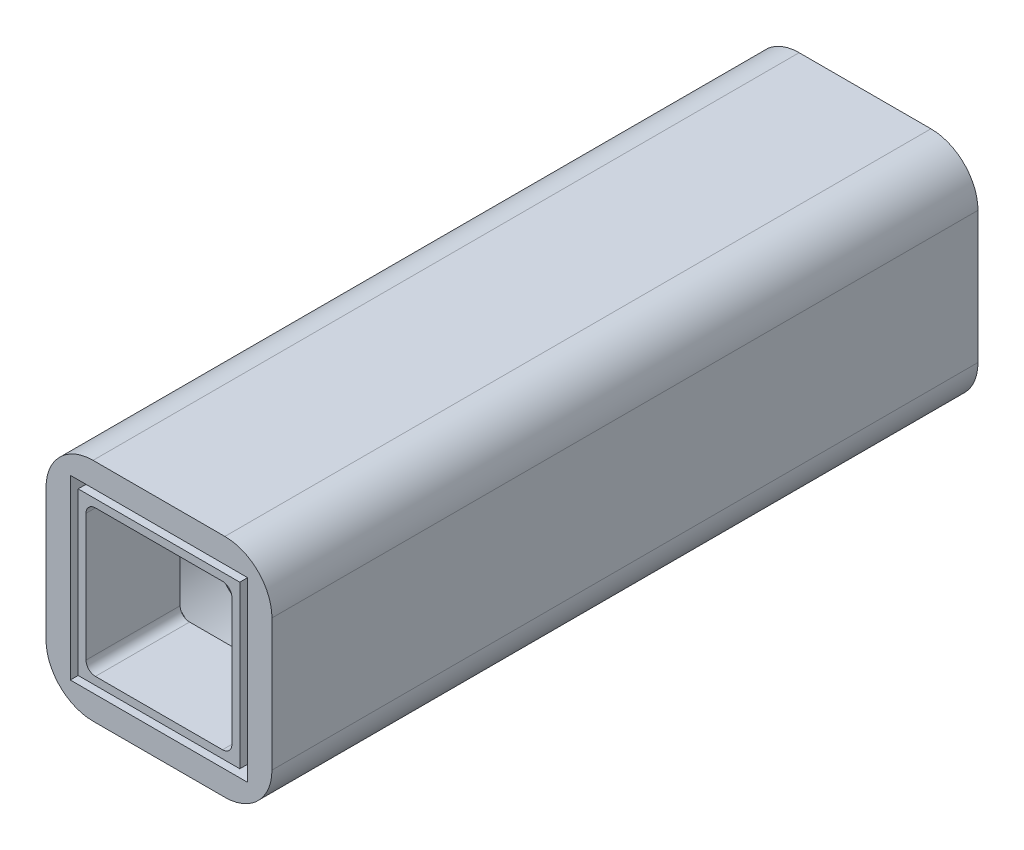
SolidWorks part; units mm, degrees
ref_plane "Front Plane" through (0, 0, 0) normal (0, 0, 1) x (1, 0, 0)
ref_plane "Top Plane" through (0, 0, 0) normal (0, 1, 0) x (1, 0, 0)
ref_plane "Right Plane" through (0, 0, 0) normal (1, 0, 0) x (0, 0, -1)
sketch "Sketch1" plane through (0, 0, 0) normal (0, 0, 1) x (1, 0, 0)
  circle A0 centre (0, 0) radius 26.67
  circle A1 centre (0, 0) radius 29.845
  dimension "D1" = 53.34
  dimension "D2" = 3.175
extrude "Boss-Extrude1" add sketch "Sketch1" along normal blind 165.1
sketch "Sketch2" plane through (0, 0, 0) normal (0, 1, 0) x (1, 0, 0)
  line L1 (-29.845, 0.8555) -> (29.845, 0.8555)
  line L2 (-29.845, 0.8555) -> (-29.845, -37.2445)
  line L3 (-29.845, -37.2445) -> (29.845, -37.2445)
  line L4 (29.845, 0.8555) -> (29.845, -37.2445)
  point P4 (0, 0.8555)
  dimension "D1" = 59.69
  dimension "D2" = 38.1
extrude "Cut-Extrude1" cut sketch "Sketch2" against normal through all
sketch "Sketch3" plane through (0, 0, 0) normal (0, 0, -1) x (-1, 0, 0)
  line L0 (-29.845, 0) -> (-6.985, 0)
  line L1 (6.985, 0) -> (29.845, 0)
  arc A0 (29.845, 0) -> (-29.845, 0) centre (0, 0) ccw construction
  arc A1 (29.845, 0) -> (-29.845, 0) centre (0, 0) ccw
  arc A2 (6.985, 0) -> (-6.985, 0) centre (0, 0) ccw
  dimension "D1" = 6.985
extrude "Boss-Extrude2" add sketch "Sketch3" against normal blind 6.35
sketch "Sketch4" plane through (0, 0, 165.1) normal (0, 0, 1) x (1, 0, 0)
  line L0 (0, 0) -> (0, 26.67) construction
  line L1 (1.27, 26.6397) -> (1.27, 9.45)
  line L3 (9.5173, 1.27) -> (26.6397, 1.27)
  line L4 (29.818, 1.27) -> (30.6047, 1.27)
  line L5 (0, 0) -> (26.67, 0) construction
  line L7 (9.489, -1.4654) -> (26.6397, -1.27)
  line L8 (1.27, -26.6397) -> (1.4535, -9.4251)
  line L9 (-9.3342, 1.4654) -> (-26.6397, 1.27)
  line L10 (-1.27, 26.6397) -> (-1.4773, 9.3973)
  line L11 (-1.27, -26.6397) -> (-1.4773, -9.3973)
  line L12 (-9.3342, -1.4654) -> (-26.6397, -1.27)
  arc A0 (26.67, 0) -> (-26.67, 0) centre (0, 0) ccw construction
  circle A1 centre (0, 0) radius 29.845 construction
  circle A2 centre (0, 0) radius 29.845
  arc A3 (26.6397, 1.27) -> (1.27, 26.6397) centre (0, 0) ccw
  arc A4 (26.6397, -1.27) -> (1.27, -26.6397) centre (0, 0) cw
  arc A5 (-26.6397, 1.27) -> (-1.27, 26.6397) centre (0, 0) cw
  arc A6 (-26.6397, -1.27) -> (-1.27, -26.6397) centre (0, 0) ccw
  circle A7 centre (0, 0) radius 6.985
  arc A8 (-1.4773, 9.3973) -> (-9.3342, 1.4654) centre (0.0774, 0) ccw
  arc A9 (9.5173, 1.27) -> (1.27, 9.45) centre (0.0774, 0) ccw
  arc A10 (1.4535, -9.4251) -> (9.489, -1.4654) centre (0.0774, 0) ccw
  arc A11 (-9.3342, -1.4654) -> (-1.4773, -9.3973) centre (0.0774, 0) ccw
  circle M7 centre (0, 0) radius 29.845
  circle M8 centre (0, 0) radius 26.67
  dimension "D3" = 13.97
  dimension "D2" = 19.05
  dimension "D1" = 2.54
  dimension "D4" = 2.54
sketch "Sketch5" plane through (0, 0, 0) normal (0, 0, -1) x (-1, 0, 0)
  line L0 (-29.818, 1.27) -> (-30.6047, 1.27) construction
  line L1 (-29.818, 1.27) -> (-30.6047, 1.27)
  line L2 (26.6397, -1.27) -> (9.3342, -1.4654)
  line L3 (1.4773, -9.3973) -> (1.27, -26.6397)
  line L4 (26.6397, -1.27) -> (9.3342, -1.4654)
  line L5 (1.4773, -9.3973) -> (1.27, -26.6397)
  line L6 (9.3342, 1.4654) -> (26.6397, 1.27)
  line L7 (1.27, 26.6397) -> (1.4773, 9.3973)
  line L8 (9.3342, 1.4654) -> (26.6397, 1.27)
  line L9 (1.27, 26.6397) -> (1.4773, 9.3973)
  line L10 (-9.489, -1.4654) -> (-26.6397, -1.27)
  line L11 (-1.27, -26.6397) -> (-1.4535, -9.4251)
  line L12 (-9.489, -1.4654) -> (-26.6397, -1.27)
  line L13 (-1.27, -26.6397) -> (-1.4535, -9.4251)
  line L14 (-1.27, 9.45) -> (-1.27, 26.6397)
  line L15 (-26.6397, 1.27) -> (-9.5173, 1.27)
  line L16 (-1.27, 9.45) -> (-1.27, 26.6397)
  line L17 (-26.6397, 1.27) -> (-9.5173, 1.27)
  circle A1 centre (0, 0) radius 6.985
  circle A2 centre (0, 0) radius 6.985
  circle A3 centre (0, 0) radius 29.845
  circle A4 centre (0, 0) radius 29.845
  arc A6 (1.27, -26.6397) -> (26.6397, -1.27) centre (0, 0) ccw
  arc A7 (1.4773, -9.3973) -> (9.3342, -1.4654) centre (-0.0774, 0) ccw
  arc A8 (1.27, -26.6397) -> (26.6397, -1.27) centre (0, 0) ccw
  arc A9 (1.4773, -9.3973) -> (9.3342, -1.4654) centre (-0.0774, 0) ccw
  arc A10 (26.6397, 1.27) -> (1.27, 26.6397) centre (0, 0) ccw
  arc A11 (9.3342, 1.4654) -> (1.4773, 9.3973) centre (-0.0774, 0) ccw
  arc A12 (26.6397, 1.27) -> (1.27, 26.6397) centre (0, 0) ccw
  arc A13 (9.3342, 1.4654) -> (1.4773, 9.3973) centre (-0.0774, 0) ccw
  arc A14 (-26.6397, -1.27) -> (-1.27, -26.6397) centre (0, 0) ccw
  arc A15 (-9.489, -1.4654) -> (-1.4535, -9.4251) centre (-0.0774, 0) ccw
  arc A16 (-26.6397, -1.27) -> (-1.27, -26.6397) centre (0, 0) ccw
  arc A17 (-9.489, -1.4654) -> (-1.4535, -9.4251) centre (-0.0774, 0) ccw
  arc A18 (-1.27, 26.6397) -> (-26.6397, 1.27) centre (0, 0) ccw
  arc A19 (-1.27, 9.45) -> (-9.5173, 1.27) centre (-0.0774, 0) ccw
  arc A20 (-1.27, 26.6397) -> (-26.6397, 1.27) centre (0, 0) ccw
  arc A21 (-1.27, 9.45) -> (-9.5173, 1.27) centre (-0.0774, 0) ccw
  arc M19 (29.845, 0) -> (-29.845, 0) centre (0, 0) ccw
  line M20 (-29.845, 0) -> (-6.985, 0)
  arc M21 (-6.985, 0) -> (6.985, 0) centre (0, 0) cw
  line M22 (6.985, 0) -> (29.845, 0)
  dimension "D1" = 0
  dimension "D2" = 0
  dimension "D3" = 0
  dimension "D4" = 0
  dimension "D5" = 0
  dimension "D6" = 0
extrude "Boss-Extrude4" add sketch "Sketch5" against normal blind 6.35 contours A20 L16 L9 A12 L8 L17 M21 M22 M19 M20 | L16 A21 L17 A4 L8 A13 L9 A2 L5 A9 L4 A8 L12 A17 L13 A16 M21 M20 M22 | A17 L12 A16 L13 | A9 L5 A8 L4 | A13 L8 A12 L9 | A21 L16 A20 L17 region at (-12.7089, -12.7031, 0) region at (-12.7089, 12.7031, 0) region at (12.719, -12.7249, 0) region at (12.6879, 12.6906, 0) region at (0.0199, -14.2557, 0) region at (-0.0428, 14.3018, 0)
extrude "Boss-Extrude5" add sketch "Sketch4" against normal blind 6.35 contours M7 M8 | L12 A11 L11 L8 A10 L7 L3 A9 L1 L10 A8 L9 A7 M8 region at (0.5157, 18.0449, 165.1) region at (-28.9943, -0.6172, 165.1)
sketch "Sketch6" plane through (0, 0, 0) normal (0, 0, 1) x (1, 0, 0)
  line L1 (30.48, -30.48) -> (-30.48, -30.48)
  line L2 (30.48, -30.48) -> (30.48, 30.48)
  line L3 (30.48, 30.48) -> (-30.48, 30.48)
  line L4 (-30.48, -30.48) -> (-30.48, 30.48)
  line L5 (30.48, -30.48) -> (-30.48, 30.48) construction
  line L6 (30.48, 30.48) -> (-30.48, -30.48) construction
  circle A1 centre (0, 0) radius 29.845
  point P0 (0, 0)
extrude "Boss-Extrude7" add sketch "Sketch6" along normal blind 190.5
sketch "Sketch7" plane through (0, 0, 190.5) normal (0, 0, 1) x (1, 0, 0)
  line L1 (-19.685, -19.685) -> (19.685, -19.685)
  line L2 (-19.685, -19.685) -> (-19.685, 19.685)
  line L3 (-19.685, 19.685) -> (19.685, 19.685)
  line L4 (19.685, -19.685) -> (19.685, 19.685)
  line L5 (-19.685, -19.685) -> (19.685, 19.685) construction
  line L6 (-19.685, 19.685) -> (19.685, -19.685) construction
  point P0 (0, 0)
  line M5 (-30.48, 30.48) -> (-30.48, -30.48)
  line M6 (-30.48, -30.48) -> (30.48, -30.48)
  line M7 (30.48, -30.48) -> (30.48, 30.48)
  line M8 (30.48, 30.48) -> (-30.48, 30.48)
  circle M9 centre (0, 0) radius 29.845
  dimension "D1" = 39.37
  dimension "D2" = 39.37
extrude "Boss-Extrude8" add sketch "Sketch7" against normal blind 25.4 contours M8 M5 M6 M7 M9 | L4 L1 L2 L3 M9 region at (0, 30.3938, 190.5) region at (-29.0009, 0, 190.5)
sketch "Sketch8" plane through (0, 0, 190.5) normal (0, 0, 1) x (1, 0, 0)
  line L1 (26.035, -26.035) -> (-26.035, -26.035)
  line L2 (26.035, -26.035) -> (26.035, 26.035)
  line L3 (26.035, 26.035) -> (-26.035, 26.035)
  line L4 (-26.035, -26.035) -> (-26.035, 26.035)
  line L5 (26.035, -26.035) -> (-26.035, 26.035) construction
  line L6 (26.035, 26.035) -> (-26.035, -26.035) construction
  line L7 (19.685, -19.685) -> (-19.685, -19.685)
  line L8 (19.685, -19.685) -> (19.685, 19.685)
  line L9 (19.685, 19.685) -> (-19.685, 19.685)
  line L10 (-19.685, -19.685) -> (-19.685, 19.685)
  line L11 (19.685, -19.685) -> (-19.685, 19.685) construction
  line L12 (19.685, 19.685) -> (-19.685, -19.685) construction
  line L13 (23.9184, -23.9184) -> (-23.9184, -23.9184)
  line L14 (23.9184, -23.9184) -> (23.9184, 23.9184)
  line L15 (23.9184, 23.9184) -> (-23.9184, 23.9184)
  line L16 (-23.9184, -23.9184) -> (-23.9184, 23.9184)
  line L17 (23.9184, -23.9184) -> (-23.9184, 23.9184) construction
  line L18 (23.9184, 23.9184) -> (-23.9184, -23.9184) construction
  line L19 (21.8018, -21.8018) -> (-21.8018, -21.8018)
  line L20 (21.8018, -21.8018) -> (21.8018, 21.8018)
  line L21 (21.8018, 21.8018) -> (-21.8018, 21.8018)
  line L22 (-21.8018, -21.8018) -> (-21.8018, 21.8018)
  line L23 (21.8018, -21.8018) -> (-21.8018, 21.8018) construction
  line L24 (21.8018, 21.8018) -> (-21.8018, -21.8018) construction
  point P0 (0, 0)
  point P6 (0, 0)
  point P12 (0, 0)
  point P17 (0, 0)
  dimension "D1" = 52.07
  dimension "D2" = 52.07
  dimension "D3" = 2.1166
  dimension "D4" = 2.1166
extrude "Cut-Extrude2" cut sketch "Sketch8" against normal blind 12.7 contours L16 L13 L14 L15 L19 L22 L21 L20 region at (0, -23.2419, 190.5)
fillet "Fillet1" radius 2.54 4 edges at (19.685, 19.685, 177.8) (19.685, -19.685, 177.8) (-19.685, -19.685, 177.8) (-19.685, 19.685, 177.8)
fillet "Fillet2" radius 12.7 4 edges at (-30.48, -30.48, 95.25) (-30.48, 30.48, 95.25) (30.48, -30.48, 95.25) (30.48, 30.48, 95.25)
